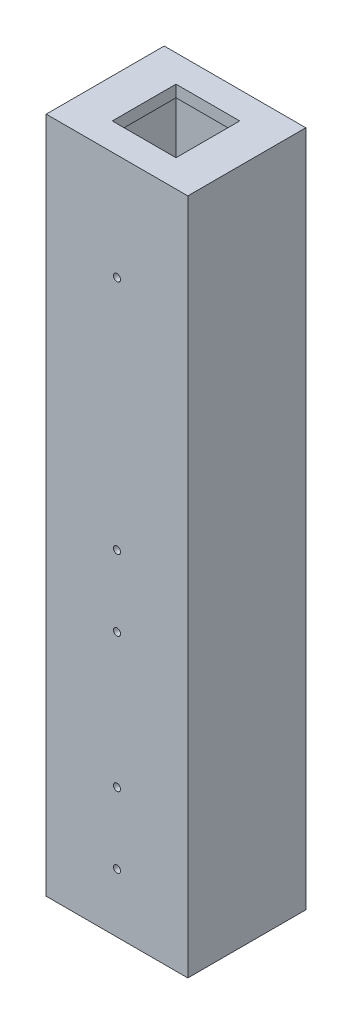
SolidWorks part; units mm, degrees
ref_plane "前视基准面" through (0, 0, 0) normal (0, 0, 1) x (1, 0, 0)
ref_plane "上视基准面" through (0, 0, 0) normal (0, 1, 0) x (1, 0, 0)
ref_plane "右视基准面" through (0, 0, 0) normal (1, 0, 0) x (0, 0, -1)
other "Configuration Table"
sketch "草图1" plane through (0, 0, 0) normal (0, 1, 0) x (1, 0, 0)
  line L1 (-3.1, 3.1) -> (3.1, 3.1)
  line L2 (-3.1, 3.1) -> (-3.1, -3.1)
  line L3 (-3.1, -3.1) -> (3.1, -3.1)
  line L4 (3.1, 3.1) -> (3.1, -3.1)
  line L5 (-3.1, 3.1) -> (3.1, -3.1) construction
  line L6 (-3.1, -3.1) -> (3.1, 3.1) construction
  line L7 (-6, 5) -> (6, 5)
  line L8 (-6, 5) -> (-6, -5)
  line L9 (-6, -5) -> (6, -5)
  line L10 (6, 5) -> (6, -5)
  line L11 (-6, 5) -> (6, -5) construction
  line L12 (-6, -5) -> (6, 5) construction
  line L13 (-2.7, -2.7) -> (2.7, -2.7)
  line L14 (-2.7, -2.7) -> (-2.7, 2.7)
  line L15 (-2.7, 2.7) -> (2.7, 2.7)
  line L16 (2.7, -2.7) -> (2.7, 2.7)
  line L17 (-2.7, -2.7) -> (2.7, 2.7) construction
  line L18 (-2.7, 2.7) -> (2.7, -2.7) construction
  point P0 (0, 0)
  point P5 (0, 0)
  point P13 (0, 0)
  dimension "D1" = 6.2
  dimension "D2" = 10
  dimension "D3" = 5.4
  dimension "D4" = 12
extrude "凸台-拉伸1" add sketch "草图1" along normal blind 54 contours L10 L7 L8 L9 L1 L4 L3 L2 region at (0, 0, -4.8438)
extrude "凸台-拉伸2" add sketch "草图1<3>" against normal blind 1 from surface contours L10 L7 L8 L9 L1 L4 L3 L2 | L4 L1 L2 L3 L16 L13 L14 L15 region at (0, 0, -3.0123) region at (0, 0, -4.8438) starting at face at (0, 54, 0)
sketch "草图1<3>" plane through (0, 0, 0) normal (0, 1, 0) x (1, 0, 0) same geometry as "草图1"
sketch "草图3" plane through (0, 0, 0) normal (0, -1, 0) x (1, 0, 0)
  line L1 (-3.6, 3.6) -> (3.6, 3.6)
  line L2 (-3.6, 3.6) -> (-3.6, -3.6)
  line L3 (-3.6, -3.6) -> (3.6, -3.6)
  line L4 (3.6, 3.6) -> (3.6, -3.6)
  line L5 (-3.6, 3.6) -> (3.6, -3.6) construction
  line L6 (-3.6, -3.6) -> (3.6, 3.6) construction
  line L7 (-6, 5) -> (6, 5)
  line L8 (-6, 5) -> (-6, -5)
  line L9 (-6, -5) -> (6, -5)
  line L10 (6, 5) -> (6, -5)
  point P0 (0, 0)
  dimension "D1" = 7.2
extrude "凸台-拉伸3" add sketch "草图3" along normal blind 3.4 contours L8 L9 L10 L7 | L2 L3 L4 L1
sketch "草图2" plane through (0, -3.4, 0) normal (0, -1, 0) x (1, 0, 0)
  line L0 (-6, -5) -> (-6, 5) construction
  line L8 (-6, 5) -> (6, 5) construction
  line L9 (-6, -5) -> (6, -5) construction
  line L10 (6, -5) -> (6, 5) construction
  circle A0 centre (-4.5, 3.5) radius 0.3
  circle A1 centre (4.5, -3.5) radius 0.3
  circle A2 centre (4.5, 3.5) radius 0.3
  circle A3 centre (-4.5, -3.5) radius 0.3
  point P0 (0, 0)
  dimension "D2" = 0.6
  dimension "D3" = 1.5
  dimension "D4" = 1.5
  dimension "D5" = 1.5
  dimension "D6" = 1.5
extrude "切除-拉伸1" cut sketch "草图2" against normal blind 2 contours A0 | A2 | A3 | A1
sketch "草图7" plane through (0, 0, -5) normal (0, 0, -1) x (-1, 0, 0)
  line L0 (0, 54) -> (0, -3.4)
  line L1 (6, 54) -> (-6, 54) construction
  line L2 (6, -3.4) -> (-6, -3.4) construction
  circle A0 centre (0, 19) radius 0.3
  circle A1 centre (0, 25) radius 0.3
  circle A2 centre (0, 45) radius 0.3
  dimension "D1" = 0.6
  dimension "D2" = 22.4
  dimension "D3" = 6
  dimension "D4" = 20
extrude "切除-拉伸2" cut sketch "草图7" against normal through all contours A0 | A1 | A2
sketch "草图8" plane through (0, 0, -5) normal (0, 0, -1) x (-1, 0, 0)
  line L0 (6, -3.4) -> (-6, -3.4) construction
  circle A0 centre (0, 1.6) radius 0.3
  circle A1 centre (0, 7.6) radius 0.3
  point P4 (0, 0)
  point P6 (0, 0)
  point P7 (0, 0)
  dimension "D1" = 0.6
  dimension "D2" = 6
  dimension "D3" = 5
extrude "切除-拉伸3" cut sketch "草图8" against normal through all
